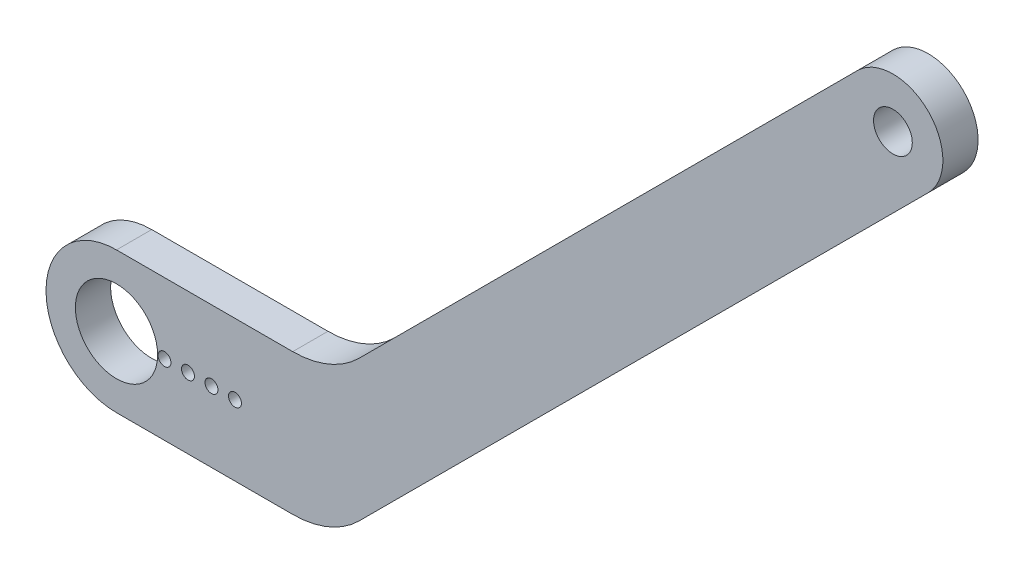
SolidWorks part; units mm, degrees
ref_plane "前视基准面" through (0, 0, 0) normal (0, 0, 1) x (1, 0, 0)
ref_plane "上视基准面" through (0, 0, 0) normal (0, 1, 0) x (1, 0, 0)
ref_plane "右视基准面" through (0, 0, 0) normal (1, 0, 0) x (0, 0, -1)
sketch "草图1" plane through (0, 0, 0) normal (0, 0, 1) x (1, 0, 0)
  line L2 (0.0002, 5.9998) -> (14.9998, 5.9998)
  line L3 (0.0002, -6.0002) -> (14.9919, -6.0002)
  line L6 (20.647, -3.6588) -> (69.0937, 44.7591)
  line L12 (63.0833, 50.7696) -> (20.6569, 8.3431)
  arc A1 (0.0002, 5.9998) -> (0.0002, -6.0002) centre (0.0002, -0.0002) ccw
  arc A2 (14.9998, 5.9998) -> (20.6569, 8.3431) centre (14.9998, 13.9998) ccw
  arc A3 (14.9919, -6.0002) -> (20.647, -3.6588) centre (14.9919, 1.9998) ccw
  arc A8 (63.0833, 50.7696) -> (69.0937, 44.7591) centre (66.0885, 47.7643) cw
  point P11 (0, 0)
  point P12 (54.9515, 30.1604)
extrude "凸台-拉伸1" add sketch "草图1" along normal blind 3 contours L3 A3 L6 L12 A2 L2 A1 region at (31.8905, 17.1457, 0)
sketch "草图9" plane through (0, 0, 3) normal (0, 0, 1) x (1, 0, 0)
  line L17 (2.1682, 2.7475) -> (14.2, 1.5587)
  line L18 (2.1682, -2.7475) -> (14.2, -1.9413)
  circle A0 centre (0, 0) radius 3.5
  circle A1 centre (66.0885, 47.7643) radius 1.65
  arc A2 (14.2, 1.5587) -> (14.2, -1.9413) centre (14.0271, -0.1913) cw
  point P5 (66.0885, 47.7643)
extrude "切除-拉伸5" cut sketch "草图9" against normal blind 6 contours A0 | A1 region at (0, 0, 3)
extrude "切除-拉伸7" cut sketch "草图9<4>" against normal through all from offset 1 contours A2 L17 A0 L18 region at (8.7898, -0.1052, 3) offset against normal yes
sketch "草图9<4>" plane through (0, 0, 3) normal (0, 0, 1) x (1, 0, 0) same geometry as "草图9"
ref_plane "基准面1" through (0, 0, 3) normal (0, 0, 1) x (1, 0, 0)
sketch "草图13" plane through (0, 0, 3) normal (0, 0, 1) x (1, 0, 0)
  circle A0 centre (4.085, 0) radius 0.55
  circle A1 centre (6.085, 0) radius 0.55
  circle A2 centre (8.085, 0) radius 0.55
  circle A3 centre (10.085, 0) radius 0.55
  dimension "D1" = 4
extrude "切除-拉伸10" cut sketch "草图13" against normal through all
